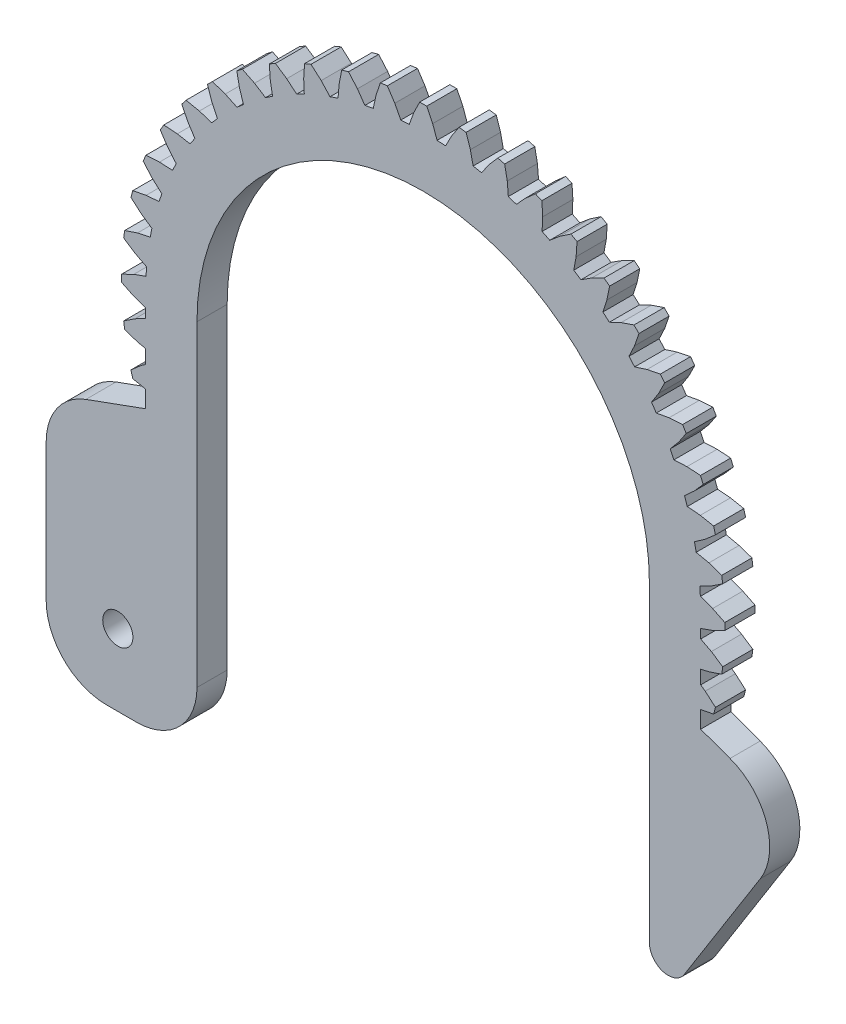
SolidWorks part; units mm, degrees
material "Delrin 2700 NC010, Low Viscosity Acetal Copolymer (SS)"
ref_plane "Front Plane" through (0, 0, 0) normal (0, 0, 1) x (1, 0, 0)
ref_plane "Top Plane" through (0, 0, 0) normal (0, 1, 0) x (1, 0, 0)
ref_plane "Right Plane" through (0, 0, 0) normal (1, 0, 0) x (0, 0, -1)
sketch "Sketch1" plane through (0, 0, 0) normal (0, 0, 1) x (1, 0, 0)
  line L0 (83.8835, 67.191) -> (85.5092, 66.6061)
  line L1 (85.5092, 66.6061) -> (87.1271, 65.8138)
  line L2 (87.1271, 65.8138) -> (87.1271, 64.8854)
  line L3 (87.1271, 64.8854) -> (85.5092, 64.0931)
  line L4 (85.5092, 64.0931) -> (83.8835, 63.5083)
  line L5 (83.8835, 63.5083) -> (83.8095, 62.3776)
  line L6 (83.8095, 62.3776) -> (85.3448, 61.5855)
  line L7 (85.3448, 61.5855) -> (86.8456, 60.5888)
  line L8 (86.8456, 60.5888) -> (86.7243, 59.6683)
  line L9 (86.7243, 59.6683) -> (85.0168, 59.094)
  line L10 (85.0168, 59.094) -> (83.3288, 58.7263)
  line L11 (83.3288, 58.7263) -> (83.1077, 57.615)
  line L12 (83.1077, 57.615) -> (84.5266, 56.6293)
  line L13 (84.5266, 56.6293) -> (85.8844, 55.4453)
  line L14 (85.8844, 55.4453) -> (85.6441, 54.5485)
  line L15 (85.6441, 54.5485) -> (83.8761, 54.202)
  line L16 (83.8761, 54.202) -> (82.1545, 54.0577)
  line L17 (82.1545, 54.0577) -> (81.7903, 52.9848)
  line L18 (81.7903, 52.9848) -> (83.0684, 51.8222)
  line L19 (83.0684, 51.8222) -> (84.26, 50.4711)
  line L20 (84.26, 50.4711) -> (83.9048, 49.6134)
  line L21 (83.9048, 49.6134) -> (82.1066, 49.5006)
  line L22 (82.1066, 49.5006) -> (80.3809, 49.5823)
  line L23 (80.3809, 49.5823) -> (79.8799, 48.5661)
  line L24 (79.8799, 48.5661) -> (80.9952, 47.2468)
  line L25 (80.9952, 47.2468) -> (82.0003, 45.7516)
  line L26 (82.0003, 45.7516) -> (81.5361, 44.9476)
  line L27 (81.5361, 44.9476) -> (79.7387, 45.0704)
  line L28 (79.7387, 45.0704) -> (78.0384, 45.3766)
  line L29 (78.0384, 45.3766) -> (77.4089, 44.4346)
  line L30 (77.4089, 44.4346) -> (78.3426, 42.9809)
  line L31 (78.3426, 42.9809) -> (79.1439, 41.3674)
  line L32 (79.1439, 41.3674) -> (78.5788, 40.6309)
  line L33 (78.5788, 40.6309) -> (76.8128, 40.9873)
  line L34 (76.8128, 40.9873) -> (75.167, 41.5128)
  line L35 (75.167, 41.5128) -> (74.4199, 40.6609)
  line L36 (74.4199, 40.6609) -> (75.1558, 39.0979)
  line L37 (75.1558, 39.0979) -> (75.7397, 37.3936)
  line L38 (75.7397, 37.3936) -> (75.0832, 36.737)
  line L39 (75.0832, 36.737) -> (73.3788, 37.3209)
  line L40 (73.3788, 37.3209) -> (71.8158, 38.0569)
  line L41 (71.8158, 38.0569) -> (70.9639, 37.3097)
  line L42 (70.9639, 37.3097) -> (71.4895, 35.6639)
  line L43 (71.4895, 35.6639) -> (71.8459, 33.898)
  line L44 (71.8459, 33.898) -> (71.1093, 33.3328)
  line L45 (71.1093, 33.3328) -> (69.4958, 34.1341)
  line L46 (69.4958, 34.1341) -> (68.0421, 35.0679)
  line L47 (68.0421, 35.0679) -> (67.1001, 34.4384)
  line L48 (67.1001, 34.4384) -> (67.4064, 32.738)
  line L49 (67.4064, 32.738) -> (67.5292, 30.9407)
  line L50 (67.5292, 30.9407) -> (66.7251, 30.4764)
  line L51 (66.7251, 30.4764) -> (65.23, 31.4815)
  line L52 (65.23, 31.4815) -> (63.9107, 32.5969)
  line L53 (63.9107, 32.5969) -> (62.8945, 32.0958)
  line L54 (62.8945, 32.0958) -> (62.9762, 30.3701)
  line L55 (62.9762, 30.3701) -> (62.8633, 28.572)
  line L56 (62.8633, 28.572) -> (62.0056, 28.2167)
  line L57 (62.0056, 28.2167) -> (60.6545, 29.4083)
  line L58 (60.6545, 29.4083) -> (59.4919, 30.6864)
  line L59 (59.4919, 30.6864) -> (58.419, 30.3222)
  line L60 (58.419, 30.3222) -> (58.2748, 28.6006)
  line L61 (58.2748, 28.6006) -> (57.9283, 26.8327)
  line L62 (57.9283, 26.8327) -> (57.0315, 26.5924)
  line L63 (57.0315, 26.5924) -> (55.8474, 27.9502)
  line L64 (55.8474, 27.9502) -> (54.8618, 29.369)
  line L65 (54.8618, 29.369) -> (53.7504, 29.1479)
  line L66 (53.7504, 29.1479) -> (53.3827, 27.4599)
  line L67 (53.3827, 27.4599) -> (52.8084, 25.7524)
  line L68 (52.8084, 25.7524) -> (51.888, 25.6311)
  line L69 (51.888, 25.6311) -> (50.8913, 27.1319)
  line L70 (50.8913, 27.1319) -> (50.0992, 28.6672)
  line L71 (50.0992, 28.6672) -> (48.9685, 28.5932)
  line L72 (48.9685, 28.5932) -> (48.3836, 26.9675)
  line L73 (48.3836, 26.9675) -> (47.5914, 25.3496)
  line L74 (47.5914, 25.3496) -> (46.6629, 25.3496)
  line L75 (46.6629, 25.3496) -> (45.8707, 26.9675)
  line L76 (45.8707, 26.9675) -> (45.2858, 28.5932)
  line L77 (45.2858, 28.5932) -> (44.1551, 28.6672)
  line L78 (44.1551, 28.6672) -> (43.363, 27.1319)
  line L79 (43.363, 27.1319) -> (42.3663, 25.6311)
  line L80 (42.3663, 25.6311) -> (41.4459, 25.7524)
  line L81 (41.4459, 25.7524) -> (40.8715, 27.4599)
  line L82 (40.8715, 27.4599) -> (40.5038, 29.1479)
  line L83 (40.5038, 29.1479) -> (39.3925, 29.369)
  line L84 (39.3925, 29.369) -> (38.4068, 27.9502)
  line L85 (38.4068, 27.9502) -> (37.2228, 26.5924)
  line L86 (37.2228, 26.5924) -> (36.326, 26.8327)
  line L87 (36.326, 26.8327) -> (35.9795, 28.6006)
  line L88 (35.9795, 28.6006) -> (35.8352, 30.3222)
  line L89 (35.8352, 30.3222) -> (34.7624, 30.6864)
  line L90 (34.7624, 30.6864) -> (33.5998, 29.4083)
  line L91 (33.5998, 29.4083) -> (32.2487, 28.2167)
  line L92 (32.2487, 28.2167) -> (31.3909, 28.572)
  line L93 (31.3909, 28.572) -> (31.2781, 30.3701)
  line L94 (31.2781, 30.3701) -> (31.3598, 32.0958)
  line L95 (31.3598, 32.0958) -> (30.3436, 32.5969)
  line L96 (30.3436, 32.5969) -> (29.0243, 31.4815)
  line L97 (29.0243, 31.4815) -> (27.5292, 30.4764)
  line L98 (27.5292, 30.4764) -> (26.7251, 30.9407)
  line L99 (26.7251, 30.9407) -> (26.8479, 32.738)
  line L100 (26.8479, 32.738) -> (27.1541, 34.4384)
  line L101 (27.1541, 34.4384) -> (26.2121, 35.0679)
  line L102 (26.2121, 35.0679) -> (24.7585, 34.1341)
  line L103 (24.7585, 34.1341) -> (23.1449, 33.3328)
  line L104 (23.1449, 33.3328) -> (22.4084, 33.898)
  line L105 (22.4084, 33.898) -> (22.7648, 35.6639)
  line L106 (22.7648, 35.6639) -> (23.2904, 37.3097)
  line L107 (23.2904, 37.3097) -> (22.4384, 38.0569)
  line L108 (22.4384, 38.0569) -> (20.8754, 37.3209)
  line L109 (20.8754, 37.3209) -> (19.1711, 36.737)
  line L110 (19.1711, 36.737) -> (18.5146, 37.3936)
  line L111 (18.5146, 37.3936) -> (19.0984, 39.0979)
  line L112 (19.0984, 39.0979) -> (19.8344, 40.6609)
  line L113 (19.8344, 40.6609) -> (19.0872, 41.5128)
  line L114 (19.0872, 41.5128) -> (17.4414, 40.9873)
  line L115 (17.4414, 40.9873) -> (15.6755, 40.6309)
  line L116 (15.6755, 40.6309) -> (15.1103, 41.3674)
  line L117 (15.1103, 41.3674) -> (15.9116, 42.9809)
  line L118 (15.9116, 42.9809) -> (16.8454, 44.4346)
  line L119 (16.8454, 44.4346) -> (16.2159, 45.3766)
  line L120 (16.2159, 45.3766) -> (14.5155, 45.0704)
  line L121 (14.5155, 45.0704) -> (12.7182, 44.9476)
  line L122 (12.7182, 44.9476) -> (12.2539, 45.7516)
  line L123 (12.2539, 45.7516) -> (13.2591, 47.2468)
  line L124 (13.2591, 47.2468) -> (14.3744, 48.5661)
  line L125 (14.3744, 48.5661) -> (13.8733, 49.5823)
  line L126 (13.8733, 49.5823) -> (12.1476, 49.5006)
  line L127 (12.1476, 49.5006) -> (10.3495, 49.6134)
  line L128 (10.3495, 49.6134) -> (9.9942, 50.4711)
  line L129 (9.9942, 50.4711) -> (11.1858, 51.8222)
  line L130 (11.1858, 51.8222) -> (12.4639, 52.9848)
  line L131 (12.4639, 52.9848) -> (12.0997, 54.0577)
  line L132 (12.0997, 54.0577) -> (10.3781, 54.202)
  line L133 (10.3781, 54.202) -> (8.6102, 54.5485)
  line L134 (8.6102, 54.5485) -> (8.3699, 55.4453)
  line L135 (8.3699, 55.4453) -> (9.7277, 56.6293)
  line L136 (9.7277, 56.6293) -> (11.1465, 57.615)
  line L137 (11.1465, 57.615) -> (10.9255, 58.7263)
  line L138 (10.9255, 58.7263) -> (9.2374, 59.094)
  line L139 (9.2374, 59.094) -> (7.5299, 59.6683)
  line L140 (7.5299, 59.6683) -> (7.4086, 60.5888)
  line L141 (7.4086, 60.5888) -> (8.9094, 61.5855)
  line L142 (8.9094, 61.5855) -> (10.4448, 62.3776)
  line L143 (10.4448, 62.3776) -> (10.3707, 63.5083)
  line L144 (10.3707, 63.5083) -> (8.745, 64.0931)
  line L145 (8.745, 64.0931) -> (7.1271, 64.8854)
  line L146 (7.1271, 64.8854) -> (7.1271, 65.8138)
  line L147 (7.1271, 65.8138) -> (8.745, 66.6061)
  line L148 (8.745, 66.6061) -> (10.3707, 67.191)
  line L149 (10.3707, 67.191) -> (10.4448, 68.3216)
  line L150 (10.4448, 68.3216) -> (8.9094, 69.1138)
  line L151 (8.9094, 69.1138) -> (7.4086, 70.1105)
  line L152 (7.4086, 70.1105) -> (7.5299, 71.0309)
  line L153 (7.5299, 71.0309) -> (9.2374, 71.6052)
  line L154 (9.2374, 71.6052) -> (10.9255, 71.9729)
  line L155 (10.9255, 71.9729) -> (11.1465, 73.0842)
  line L156 (11.1465, 73.0842) -> (9.7277, 74.0699)
  line L157 (9.7277, 74.0699) -> (8.3699, 75.254)
  line L158 (8.3699, 75.254) -> (8.6102, 76.1508)
  line L159 (8.6102, 76.1508) -> (10.3781, 76.4973)
  line L160 (10.3781, 76.4973) -> (12.0997, 76.6415)
  line L161 (12.0997, 76.6415) -> (12.4639, 77.7144)
  line L162 (12.4639, 77.7144) -> (11.1858, 78.877)
  line L163 (11.1858, 78.877) -> (9.9942, 80.2281)
  line L164 (9.9942, 80.2281) -> (10.3495, 81.0858)
  line L165 (10.3495, 81.0858) -> (12.1476, 81.1987)
  line L166 (12.1476, 81.1987) -> (13.8733, 81.117)
  line L167 (13.8733, 81.117) -> (14.3744, 82.1332)
  line L168 (14.3744, 82.1332) -> (13.2591, 83.4525)
  line L169 (13.2591, 83.4525) -> (12.2539, 84.9476)
  line L170 (12.2539, 84.9476) -> (12.7182, 85.7516)
  line L171 (12.7182, 85.7516) -> (14.5155, 85.6289)
  line L172 (14.5155, 85.6289) -> (16.2159, 85.3226)
  line L173 (16.2159, 85.3226) -> (16.8454, 86.2646)
  line L174 (16.8454, 86.2646) -> (15.9116, 87.7183)
  line L175 (15.9116, 87.7183) -> (15.1103, 89.3318)
  line L176 (15.1103, 89.3318) -> (15.6755, 90.0684)
  line L177 (15.6755, 90.0684) -> (17.4414, 89.712)
  line L178 (17.4414, 89.712) -> (19.0872, 89.1864)
  line L179 (19.0872, 89.1864) -> (19.8344, 90.0383)
  line L180 (19.8344, 90.0383) -> (19.0984, 91.6013)
  line L181 (19.0984, 91.6013) -> (18.5146, 93.3057)
  line L182 (18.5146, 93.3057) -> (19.1711, 93.9622)
  line L183 (19.1711, 93.9622) -> (20.8754, 93.3783)
  line L184 (20.8754, 93.3783) -> (22.4384, 92.6424)
  line L185 (22.4384, 92.6424) -> (23.2904, 93.3895)
  line L186 (23.2904, 93.3895) -> (22.7648, 95.0353)
  line L187 (22.7648, 95.0353) -> (22.4084, 96.8013)
  line L188 (22.4084, 96.8013) -> (23.1449, 97.3664)
  line L189 (23.1449, 97.3664) -> (24.7585, 96.5651)
  line L190 (24.7585, 96.5651) -> (26.2121, 95.6314)
  line L191 (26.2121, 95.6314) -> (27.1541, 96.2609)
  line L192 (27.1541, 96.2609) -> (26.8479, 97.9612)
  line L193 (26.8479, 97.9612) -> (26.7251, 99.7586)
  line L194 (26.7251, 99.7586) -> (27.5292, 100.2228)
  line L195 (27.5292, 100.2228) -> (29.0243, 99.2177)
  line L196 (29.0243, 99.2177) -> (30.3436, 98.1023)
  line L197 (30.3436, 98.1023) -> (31.3598, 98.6034)
  line L198 (31.3598, 98.6034) -> (31.2781, 100.3291)
  line L199 (31.2781, 100.3291) -> (31.3909, 102.1272)
  line L200 (31.3909, 102.1272) -> (32.2487, 102.4825)
  line L201 (32.2487, 102.4825) -> (33.5998, 101.2909)
  line L202 (33.5998, 101.2909) -> (34.7624, 100.0128)
  line L203 (34.7624, 100.0128) -> (35.8352, 100.377)
  line L204 (35.8352, 100.377) -> (35.9795, 102.0986)
  line L205 (35.9795, 102.0986) -> (36.326, 103.8666)
  line L206 (36.326, 103.8666) -> (37.2228, 104.1068)
  line L207 (37.2228, 104.1068) -> (38.4068, 102.7491)
  line L208 (38.4068, 102.7491) -> (39.3925, 101.3302)
  line L209 (39.3925, 101.3302) -> (40.5038, 101.5513)
  line L210 (40.5038, 101.5513) -> (40.8715, 103.2393)
  line L211 (40.8715, 103.2393) -> (41.4459, 104.9468)
  line L212 (41.4459, 104.9468) -> (42.3663, 105.0681)
  line L213 (42.3663, 105.0681) -> (43.363, 103.5673)
  line L214 (43.363, 103.5673) -> (44.1551, 102.032)
  line L215 (44.1551, 102.032) -> (45.2858, 102.106)
  line L216 (45.2858, 102.106) -> (45.8707, 103.7317)
  line L217 (45.8707, 103.7317) -> (46.6629, 105.3496)
  line L218 (46.6629, 105.3496) -> (47.5914, 105.3496)
  line L219 (47.5914, 105.3496) -> (48.3836, 103.7317)
  line L220 (48.3836, 103.7317) -> (48.9685, 102.106)
  line L221 (48.9685, 102.106) -> (50.0992, 102.032)
  line L222 (50.0992, 102.032) -> (50.8913, 103.5673)
  line L223 (50.8913, 103.5673) -> (51.888, 105.0681)
  line L224 (51.888, 105.0681) -> (52.8084, 104.9468)
  line L225 (52.8084, 104.9468) -> (53.3827, 103.2393)
  line L226 (53.3827, 103.2393) -> (53.7504, 101.5513)
  line L227 (53.7504, 101.5513) -> (54.8618, 101.3302)
  line L228 (54.8618, 101.3302) -> (55.8474, 102.7491)
  line L229 (55.8474, 102.7491) -> (57.0315, 104.1068)
  line L230 (57.0315, 104.1068) -> (57.9283, 103.8666)
  line L231 (57.9283, 103.8666) -> (58.2748, 102.0986)
  line L232 (58.2748, 102.0986) -> (58.419, 100.377)
  line L233 (58.419, 100.377) -> (59.4919, 100.0128)
  line L234 (59.4919, 100.0128) -> (60.6545, 101.2909)
  line L235 (60.6545, 101.2909) -> (62.0056, 102.4825)
  line L236 (62.0056, 102.4825) -> (62.8633, 102.1272)
  line L237 (62.8633, 102.1272) -> (62.9762, 100.3291)
  line L238 (62.9762, 100.3291) -> (62.8945, 98.6034)
  line L239 (62.8945, 98.6034) -> (63.9107, 98.1023)
  line L240 (63.9107, 98.1023) -> (65.23, 99.2177)
  line L241 (65.23, 99.2177) -> (66.7251, 100.2228)
  line L242 (66.7251, 100.2228) -> (67.5292, 99.7586)
  line L243 (67.5292, 99.7586) -> (67.4064, 97.9612)
  line L244 (67.4064, 97.9612) -> (67.1001, 96.2609)
  line L245 (67.1001, 96.2609) -> (68.0421, 95.6314)
  line L246 (68.0421, 95.6314) -> (69.4958, 96.5651)
  line L247 (69.4958, 96.5651) -> (71.1093, 97.3664)
  line L248 (71.1093, 97.3664) -> (71.8459, 96.8013)
  line L249 (71.8459, 96.8013) -> (71.4895, 95.0353)
  line L250 (71.4895, 95.0353) -> (70.9639, 93.3895)
  line L251 (70.9639, 93.3895) -> (71.8158, 92.6424)
  line L252 (71.8158, 92.6424) -> (73.3788, 93.3783)
  line L253 (73.3788, 93.3783) -> (75.0832, 93.9622)
  line L254 (75.0832, 93.9622) -> (75.7397, 93.3057)
  line L255 (75.7397, 93.3057) -> (75.1558, 91.6013)
  line L256 (75.1558, 91.6013) -> (74.4199, 90.0383)
  line L257 (74.4199, 90.0383) -> (75.167, 89.1864)
  line L258 (75.167, 89.1864) -> (76.8128, 89.712)
  line L259 (76.8128, 89.712) -> (78.5788, 90.0684)
  line L260 (78.5788, 90.0684) -> (79.1439, 89.3318)
  line L261 (79.1439, 89.3318) -> (78.3426, 87.7183)
  line L262 (78.3426, 87.7183) -> (77.4089, 86.2646)
  line L263 (77.4089, 86.2646) -> (78.0384, 85.3226)
  line L264 (78.0384, 85.3226) -> (79.7387, 85.6289)
  line L265 (79.7387, 85.6289) -> (81.5361, 85.7516)
  line L266 (81.5361, 85.7516) -> (82.0003, 84.9476)
  line L267 (82.0003, 84.9476) -> (80.9952, 83.4525)
  line L268 (80.9952, 83.4525) -> (79.8799, 82.1332)
  line L269 (79.8799, 82.1332) -> (80.3809, 81.117)
  line L270 (80.3809, 81.117) -> (82.1066, 81.1987)
  line L271 (82.1066, 81.1987) -> (83.9048, 81.0858)
  line L272 (83.9048, 81.0858) -> (84.26, 80.2281)
  line L273 (84.26, 80.2281) -> (83.0684, 78.877)
  line L274 (83.0684, 78.877) -> (81.7903, 77.7144)
  line L275 (81.7903, 77.7144) -> (82.1545, 76.6415)
  line L276 (82.1545, 76.6415) -> (83.8761, 76.4973)
  line L277 (83.8761, 76.4973) -> (85.6441, 76.1508)
  line L278 (85.6441, 76.1508) -> (85.8844, 75.254)
  line L279 (85.8844, 75.254) -> (84.5266, 74.0699)
  line L280 (84.5266, 74.0699) -> (83.1077, 73.0842)
  line L281 (83.1077, 73.0842) -> (83.3288, 71.9729)
  line L282 (83.3288, 71.9729) -> (85.0168, 71.6052)
  line L283 (85.0168, 71.6052) -> (86.7243, 71.0309)
  line L284 (86.7243, 71.0309) -> (86.8456, 70.1105)
  line L285 (86.8456, 70.1105) -> (85.3448, 69.1138)
  line L286 (85.3448, 69.1138) -> (83.8095, 68.3216)
  line L287 (83.8095, 68.3216) -> (83.8835, 67.191)
  line L288 (47.1271, 105.3496) -> (47.1271, 25.3496) construction
  line L289 (7.1271, 65.3496) -> (87.1271, 65.3496) construction
  point P292 (47.1271, 65.3496)
sketch "Sketch2" plane through (0, 0, 0) normal (0, 0, 1) x (1, 0, 0)
  line L0 (-2.8729, 47.1511) -> (10.3271, 51.9555)
  line L1 (47.1271, 65.3496) -> (97.1271, 65.3496) construction
  line L2 (47.1271, 65.3496) -> (47.1271, 15.3496) construction
  line L3 (83.9271, 51.9555) -> (47.1271, 65.3496) construction
  line L4 (83.9271, 51.9555) -> (83.9271, 65.3496)
  line L5 (97.1271, 47.1511) -> (97.1271, 15.3496) construction
  line L6 (47.1271, 65.3496) -> (47.1271, 15.3496) construction
  line L7 (97.1271, 15.3496) -> (-2.8729, 15.3496)
  line L8 (-2.8729, 47.1511) -> (-2.8729, 15.3496)
  line L9 (47.1271, 65.3496) -> (97.1271, 65.3496) construction
  line L10 (7.1271, 65.3496) -> (87.1271, 65.3496) construction
  line L11 (97.1271, 47.1511) -> (83.9271, 51.9555)
  line L12 (77.1271, 15.3496) -> (97.1271, 47.1511)
  line L14 (10.3271, 51.9555) -> (10.3271, 65.3496)
  line L15 (10.3271, 65.3496) -> (83.9271, 65.3496)
  line L16 (10.3271, 51.9555) -> (47.1271, 65.3496) construction
  dimension "D1" = 100
  dimension "D2" = 50
  dimension "D3" = 20
  dimension "D4" = 20
  dimension "D5" = 36.8
sketch "Sketch3" plane through (0, 0, 0) normal (0, 0, 1) x (1, 0, 0)
  line L0 (6.6271, 24.8496) -> (-2.8729, 24.8496) construction
  line L1 (-2.8729, 47.1511) -> (-2.8729, 15.3496) construction
  line L2 (6.6271, 24.8496) -> (6.6271, 15.3496) construction
  line L3 (97.1271, 15.3496) -> (-2.8729, 15.3496) construction
  line L4 (47.1271, 65.3496) -> (47.1271, 15.3496) construction
  line L5 (7.1271, 65.3496) -> (87.1271, 65.3496) construction
  line L6 (47.1271, 65.3496) -> (97.1271, 65.3496) construction
  circle A0 centre (6.6271, 24.8496) radius 2
  circle A1 centre (87.6271, 24.8496) radius 2 construction
  dimension "D1" = 4
  dimension "D2" = 81
sketch "Sketch4" plane through (0, 0, 0) normal (0, 0, 1) x (1, 0, 0)
  circle A0 centre (47.1271, 65.3496) radius 30
  dimension "D1" = 60
extrude "Boss-Extrude1" add sketch "Sketch1" along normal blind 4
extrude "Boss-Extrude2" add sketch "Sketch2" along normal blind 4 contours L15 L14 L0 L8 L7 L11 L4 region at (43.896, 39.7571, 0)
extrude "Cut-Extrude1" cut sketch "Sketch3" along normal up to next
extrude "Cut-Extrude2" cut sketch "Sketch4" along normal up to next
sketch "Sketch5" plane through (0, 0, 0) normal (0, 0, 1) x (1, 0, 0)
  line L0 (77.1271, 65.3496) -> (77.1271, 15.3496)
  line L2 (17.1271, 65.3496) -> (17.1271, 15.3496)
  line L3 (17.1271, 15.3496) -> (77.1271, 15.3496)
  line L4 (17.1271, 65.3496) -> (77.1271, 65.3496)
  line L5 (77.1271, 15.3496) -> (-2.8729, 15.3496) construction
  circle A0 centre (47.1271, 65.3496) radius 30 construction
  dimension "D1" = 60
extrude "Cut-Extrude3" cut sketch "Sketch5" along normal up to next
fillet "Fillet1" radius 8 4 edges at (17.1271, 15.3496, 2) (-2.8729, 15.3496, 2) (-2.8729, 47.1511, 2) (97.1271, 47.1511, 2)
fillet "Fillet2" radius 2.5 1 edges at (77.1271, 15.3496, 2)
